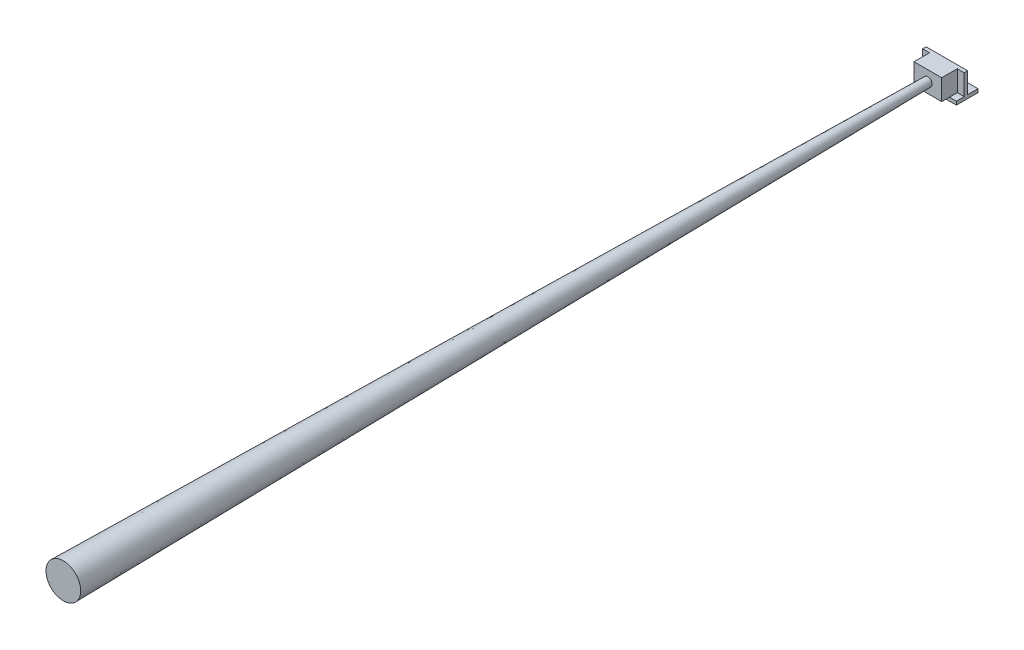
SolidWorks part; units mm, degrees
ref_plane "Front Plane" through (0, 0, 0) normal (0, 0, 1) x (1, 0, 0)
ref_plane "Top Plane" through (0, 0, 0) normal (0, 1, 0) x (1, 0, 0)
ref_plane "Right Plane" through (0, 0, 0) normal (1, 0, 0) x (0, 0, -1)
sketch "Sketch1" plane through (0, 0, 0) normal (0, 1, 0) x (1, 0, 0)
  line L1 (-24, -12.5) -> (24, -12.5)
  line L2 (-24, -12.5) -> (-24, 12.5)
  line L3 (-24, 12.5) -> (24, 12.5)
  line L4 (24, -12.5) -> (24, 12.5)
  line L5 (-24, -12.5) -> (24, 12.5) construction
  line L6 (-24, 12.5) -> (24, -12.5) construction
  point P0 (0, 0)
extrude "Boss-Extrude1" add sketch "Sketch1" along normal blind 4
sketch "Sketch2" plane through (0, 4, 0) normal (0, 1, 0) x (1, 0, 0)
  line L0 (-24, 12.5) -> (-24, -12.5) construction
  line L1 (-24, 0.5) -> (24, 0.5)
  line L2 (-24, 0.5) -> (-24, -3.5)
  line L3 (-24, -3.5) -> (24, -3.5)
  line L4 (24, 0.5) -> (24, -3.5)
  line L5 (24, -12.5) -> (24, 12.5) construction
  line L6 (-24, -12.5) -> (24, -12.5) construction
  line L7 (0, -2.2) -> (0, 2.2) construction
  line L8 (24, 12.5) -> (-24, 12.5) construction
  line L14 (-16, -3.5) -> (16, -3.5)
  line L15 (-16, -3.5) -> (-16, -21.5)
  line L16 (-16, -21.5) -> (16, -21.5)
  line L17 (16, -3.5) -> (16, -21.5)
  circle A0 centre (0, 7.5) radius 1.6
  circle A1 centre (-10, 7.5) radius 1.6
  circle A2 centre (10, 7.5) radius 1.6
  point P24 (0, -21.5)
  line M11 (24, -12.5) -> (24, 12.5)
  line M13 (-24, 12.5) -> (-24, -12.5)
  line M14 (-24, -12.5) -> (24, -12.5)
  dimension "D3" = 3.2
  dimension "D5" = 10
  dimension "D1" = 4
  dimension "D2" = 13
  dimension "D4" = 5
  dimension "D6" = 32
  dimension "D7" = 9
extrude "Boss-Extrude2" add sketch "Sketch2" along normal blind 24 contours L3 L1 M13 M11 | L17 L3 L15 M14 | L17 L15 L16 M14 region at (0, 4, 1.5) region at (0, 4, 8) region at (0, 4, 17)
extrude "Cut-Extrude1" cut sketch "Sketch2<4>" against normal up to next contours A1 | A0 | A2 region at (0, 4, -7.5) region at (-10, 4, -7.5) region at (10, 4, -7.5)
sketch "Sketch2<4>" plane through (0, 4, 0) normal (0, 1, 0) x (1, 0, 0) same geometry as "Sketch2"
sketch "Sketch3" plane through (0, 0, 0) normal (1, 0, 0) x (0, 0, -1)
  line L1 (-21.5, 28) -> (-21.5, 4) construction
  line L2 (-1021.5, 36.074) -> (-1021.5, 16)
  line L3 (-1021.5, 16) -> (-21.5, 16)
  line L4 (-21.5, 16) -> (-21.5, 21)
  line L5 (-21.5, 21) -> (-1021.5, 36.074)
  dimension "D2" = 1000
revolve "Revolve1" add sketch "Sketch3" angle 360 about L3
